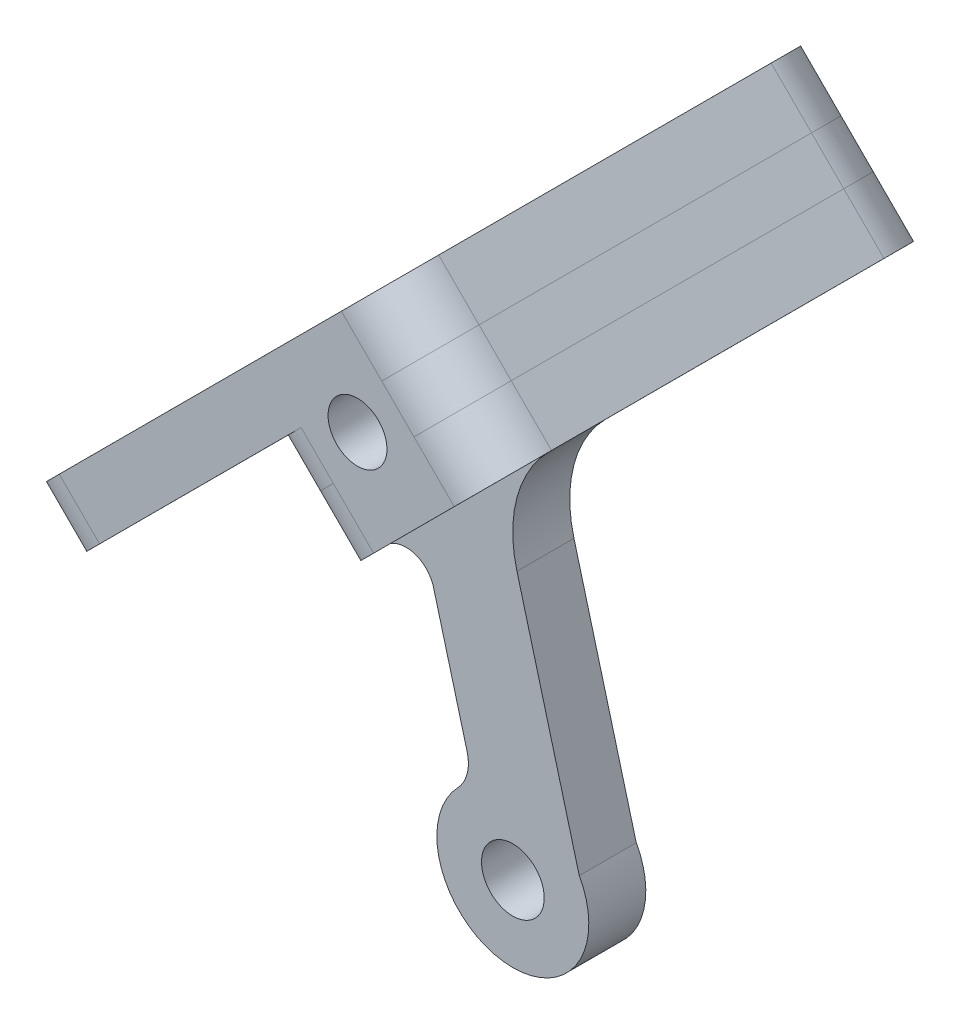
SolidWorks part; units mm, degrees
ref_plane "前视基准面" through (0, 0, 0) normal (0, 0, 1) x (1, 0, 0)
ref_plane "上视基准面" through (0, 0, 0) normal (0, 1, 0) x (1, 0, 0)
ref_plane "右视基准面" through (0, 0, 0) normal (1, 0, 0) x (0, 0, -1)
ref_plane "基准面4" through (0, 0, -3.3629) normal (0, 0, -1) x (-1, 0, 0)
sketch "草图1" plane through (0, 0, -3.3629) normal (0, 0, -1) x (-1, 0, 0)
  line L0 (-8.9295, 17.4533) -> (-12.2085, 5.2163)
  line L1 (-6.3042, 7.9338) -> (-4.5397, 14.5186)
  line L2 (-2.2643, 15.3821) -> (-0.1425, 17.5032)
  line L3 (-0.1425, 17.5032) -> (4.0998, 13.2597)
  line L4 (4.0998, 13.2597) -> (5.7975, 14.9569)
  line L5 (5.7975, 14.9569) -> (1.5545, 19.201)
  line L6 (1.5545, 19.201) -> (3.6758, 21.3217)
  line L7 (3.6758, 21.3217) -> (-4.8084, 29.8083)
  line L8 (-4.8084, 29.8083) -> (-6.932, 27.6854)
  line L9 (-6.932, 27.6854) -> (-11.1732, 31.9279)
  line L10 (-11.1732, 31.9279) -> (-12.8704, 30.2312)
  line L11 (-12.8704, 30.2312) -> (-8.6291, 25.9887)
  line L12 (-8.6291, 25.9887) -> (-10.7491, 23.8693)
  line L13 (-10.7491, 23.8693) -> (-10.6111, 23.7313)
  circle A0 centre (-3.5366, 22.594) radius 1.55
  arc A1 (-10.6111, 23.7313) -> (-8.9295, 17.4533) centre (-15.208, 19.1357) cw
  arc A2 (-12.2085, 5.2163) -> (-5.8193, 6.0355) centre (-8.7125, 3.275) ccw
  arc A3 (-5.8193, 6.0355) -> (-6.3042, 7.9338) centre (-4.3723, 7.4162) cw
  arc A4 (-4.5397, 14.5186) -> (-2.2643, 15.3821) centre (-3.0908, 14.1303) cw
  circle A5 centre (-8.7125, 3.275) radius 1.65
extrude "凸台-拉伸1" add sketch "草图1" against normal blind 3
sketch "草图2" plane through (0, 0, -0.3629) normal (0, 0, 1) x (1, 0, 0)
  line L0 (4.8084, 29.8083) -> (-3.6758, 21.3217)
  line L2 (-3.6758, 21.3217) -> (-1.5548, 19.2008)
  line L3 (10.7485, 23.8687) -> (2.2643, 15.3821)
  line L4 (-1.5545, 19.201) -> (-5.7975, 14.9569)
  line L6 (-5.7975, 14.9569) -> (-4.0998, 13.2597)
  line L7 (0.1432, 17.5038) -> (-4.0998, 13.2597)
  line L8 (11.1732, 31.9279) -> (6.932, 27.6854)
  line L9 (11.1732, 31.9279) -> (12.8704, 30.2311)
  line L11 (12.8704, 30.2311) -> (8.6291, 25.9887)
  line L12 (0.1428, 17.5034) -> (2.2643, 15.3821)
  circle A0 centre (3.5366, 22.594) radius 1.55
extrude "凸台-拉伸5" add sketch "草图2" against normal blind 20.5 and the other way blind 3
sketch "草图3" plane through (8.8235, 8.826, 0) normal (-0.707, -0.7072, 0) x (0.7072, -0.707, 0)
  line L1 (-17.6741, 2.6371) -> (-14.6746, 2.6371)
  line L2 (-17.6741, 2.6371) -> (-17.6741, -20.8629)
  line L3 (-17.6741, -20.8629) -> (-14.6746, -20.8629)
  line L4 (-14.6746, 2.6371) -> (-14.6746, -20.8629)
extrude "凸台-拉伸9" add sketch "草图3" along normal blind 15
sketch "草图4" plane through (0, 0, -20.8629) normal (0, 0, -1) x (-1, 0, 0)
  line L0 (-11.3063, 32.061) -> (-13.0034, 30.3642)
  line L1 (-11.3063, 32.061) -> (-6.932, 27.6854)
  line L2 (-13.0034, 30.3642) -> (-8.6291, 25.9887)
  line L3 (-6.932, 27.6854) -> (-8.6291, 25.9887)
extrude "切除-拉伸1" cut sketch "草图4" against normal through all
sketch "草图5" plane through (0, 0, -20.8629) normal (0, 0, -1) x (-1, 0, 0)
  line L0 (-0.1428, 17.5034) -> (4.0998, 13.2597)
  line L1 (-0.1428, 17.5034) -> (1.5549, 19.2006)
  line L2 (4.0998, 13.2597) -> (5.7975, 14.9569)
  line L3 (1.5549, 19.2006) -> (5.7975, 14.9569)
extrude "切除-拉伸2" cut sketch "草图5" against normal through all
sketch "草图6" plane through (-10.378, 10.375, 0) normal (0.7072, -0.707, 0) x (0, 0, -1)
  line L0 (9.1129, 12.4795) -> (9.1129, -2.5199)
  line L1 (-2.6371, 12.4795) -> (20.8629, 12.4795) construction
  line L2 (20.8629, -2.5199) -> (-2.6371, -2.5199) construction
  circle A0 centre (0.1129, 6.4801) radius 1.55
  circle A1 centre (18.1129, 6.4801) radius 1.55
  point P8 (18.1129, 6.4801)
  dimension "D1" = 9
  dimension "D2" = 9
extrude "切除-拉伸3" cut sketch "草图6" against normal blind 10 contours A0 | A1
fillet "圆角1" radius 3 4 edges at (-0.7061, 18.352, -20.8629) (-0.7061, 18.352, 2.6371) (1.2035, 16.4428, 2.6371) (1.2035, 16.4428, -20.8629)
fillet "圆角2" radius 3 6 edges at (5.8702, 28.7469, 2.6371) (5.8702, 28.7469, -20.8629) (7.7805, 26.837, -20.8629) (7.7805, 26.837, 2.6371) (9.6891, 24.929, 2.6371) (9.6891, 24.929, -20.8629)
fillet "圆角3" radius 3 2 edges at (-13.2202, 9.6532, -20.8629) (-13.2202, 9.6532, 2.6371)
